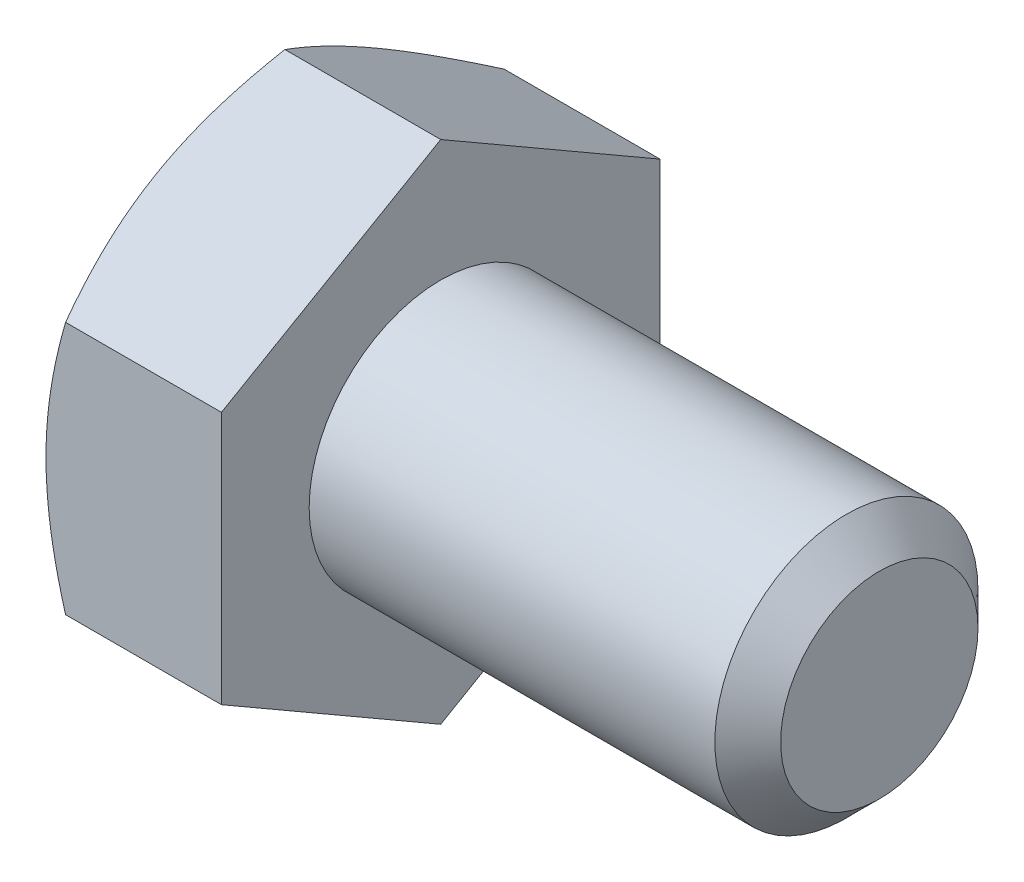
SolidWorks part; units mm, degrees
ref_plane "Front Plane" through (0, 0, 0) normal (0, 0, 1) x (1, 0, 0)
ref_plane "Top Plane" through (0, 0, 0) normal (0, 1, 0) x (1, 0, 0)
ref_plane "Right Plane" through (0, 0, 0) normal (1, 0, 0) x (0, 0, -1)
sketch "Sketch1" plane through (0, 0, 0) normal (0, 0, 1) x (1, 0, 0)
  line L0 (-7, 0) -> (7, 0) construction
  line L1 (-3, 5) -> (-3, -5) construction
  line L2 (-7, 5) -> (-7, -5) construction
  line L3 (7, 3) -> (7, -3) construction
  point P8 (3.5, -3)
  dimension "Thread Dia" = 6
  dimension "Hex" = 10
  dimension "Head Ht" = 4
  dimension "Length" = 10
  dimension "D1" = 3.5
ref_plane "Plane2" through (7, 0, 0) normal (1, 0, 0) x (0, 0, -1)
sketch "Sketch2" plane through (7, 0, 0) normal (1, 0, 0) x (0, 0, -1)
  circle A0 centre (0, 0) radius 3
extrude "Boss-Extrude1" add sketch "Sketch2" against normal up to vertex (10 mm away) up to point (-3, -5, 0)
sketch "Sketch4" plane through (7, 0, 0) normal (1, 0, 0) x (0, 0, -1)
  circle A1 centre (0, 0) radius 3
  circle A2 centre (0, 0) radius 3
  dimension "D1" = 0
curve "Helix/Spiral1" pitch 1 height 11 turns 11 parameters "Pitch"=1
chamfer "Chamfer1" distance 0.75 angle 45 1 edges at (7, 0, -3)
sketch "Sketch5" plane through (0, 0, 0) normal (0, 0, 1) x (1, 0, 0)
  line L0 (7, 3) -> (7.375, 2.3505)
  line L1 (7.375, 2.3505) -> (7.5, 2.3505)
  line L2 (7.5, 2.3505) -> (7.875, 3)
  line L3 (7, 3) -> (7.875, 3)
  line L4 (7.4375, 2.3505) -> (7.4375, 3) construction
  line L5 (7.1875, 2.6752) -> (7.6875, 2.6752) construction
  line L6 (7, -3) -> (7, 3) construction
  dimension "D1" = 60
  dimension "D2" = 0.125
  dimension "D3" = 0.5
sweep "Cut-Sweep1" [suppressed] cut profiles "Sketch5" path "Helix/Spiral1"
sketch "Sketch3" plane through (-3, 0, 0) normal (-1, 0, 0) x (0, 0, 1)
  line L0 (0, 5) -> (0, -5) construction
  line L1 (-5, -2.8868) -> (0, -5.7735)
  line L2 (0, -5.7735) -> (5, -2.8868)
  line L3 (5, -2.8868) -> (5, 2.8868)
  line L4 (5, 2.8868) -> (0, 5.7735)
  line L5 (0, 5.7735) -> (-5, 2.8868)
  line L6 (-5, 2.8868) -> (-5, -2.8868)
  circle A0 centre (0, 0) radius 5 construction
extrude "Boss-Extrude2" add sketch "Sketch3" along normal up to vertex (4 mm away) up to point (-7, -5, 0)
sketch "Sketch6" plane through (-7, 0, 0) normal (-1, 0, 0) x (0, 0, 1)
  circle A0 centre (0, 0) radius 5 construction
  circle A1 centre (0, 0) radius 5
extrude "Cut-Extrude1" cut sketch "Sketch6" against normal through all draft 60 flip side to cut
sketch "Sketch9" plane through (0, 0, 0) normal (0, 0, 1) x (1, 0, 0)
  line L0 (-3, 3) -> (-3, 0)
  line L1 (-3, 0) -> (-44, 0)
  line L2 (-44, 0) -> (-47, 3)
  line L3 (-47, 3) -> (-3, 3)
  line L4 (-7, 0) -> (7, 0) construction
  line L5 (-3, 5) -> (-3, -5) construction
  line L6 (7, 3) -> (7, -3) construction
  dimension "D1" = 45
  dimension "MinThreadLg" = 54
revolve "Revolve1" [suppressed] add sketch "Sketch9" angle 360 about L1
equation "\"D2@Sketch5\" = \"Pitch@Helix/Spiral1\"*.125"
equation "\"D3@Sketch5\" = \"Pitch@Helix/Spiral1\"*.50"
equation "\"D3@Helix/Spiral1\" = \"Length@Sketch1\"+\"Pitch@Helix/Spiral1\""
equation "\"D1@Chamfer1\" = \"Pitch@Helix/Spiral1\"*.750"
equation "\"D1@Sketch1\" = \"Pitch@Helix/Spiral1\"*3.50"
